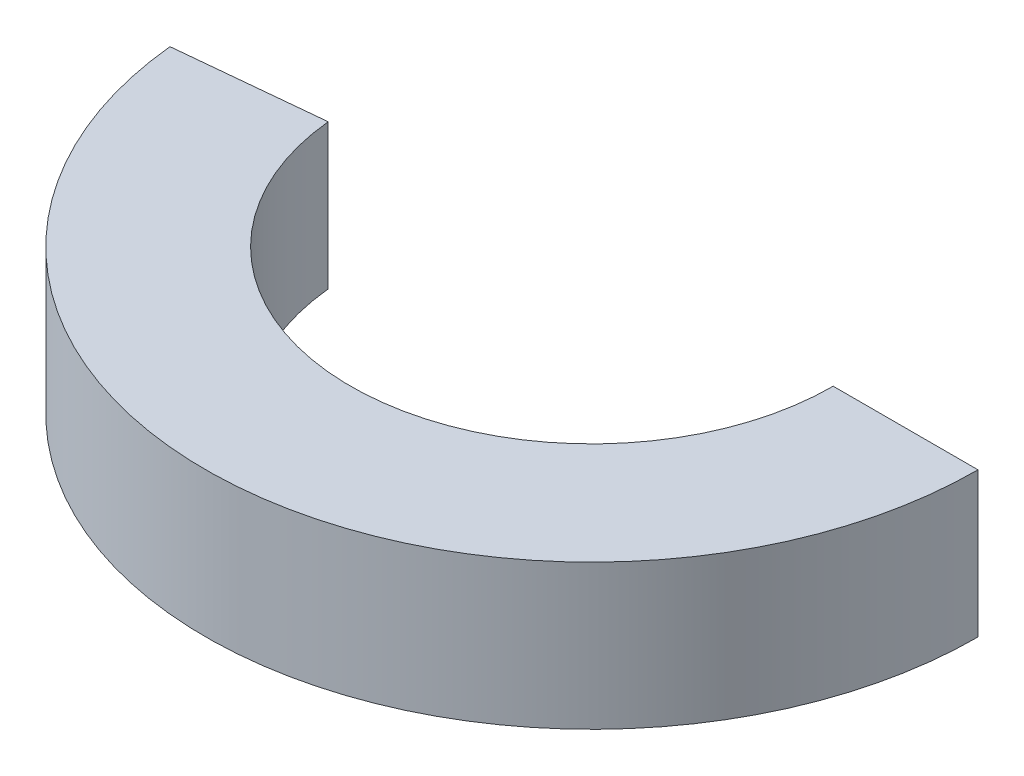
SolidWorks part; units mm, degrees
ref_plane "Front Plane" through (0, 0, 0) normal (0, 0, 1) x (1, 0, 0)
ref_plane "Top Plane" through (0, 0, 0) normal (0, 1, 0) x (1, 0, 0)
ref_plane "Right Plane" through (0, 0, 0) normal (1, 0, 0) x (0, 0, -1)
sketch "Sketch1" plane through (0, 0, 0) normal (0, 1, 0) x (1, 0, 0)
  line L0 (-39.8105, -3.8894) -> (0, 0)
  line L1 (0, 0) -> (40, 0)
  circle A0 centre (0, 0) radius 25
  circle A1 centre (0, 0) radius 40
  point P5 (0, 0)
  dimension "D1" = 15
  dimension "D2" = 80
  dimension "D3" = 174.42
extrude "Boss-Extrude1" add sketch "Sketch1" along normal blind 15 contours L0 A1 L1 A0 region at (-32.2592, 0, 4.0487)
